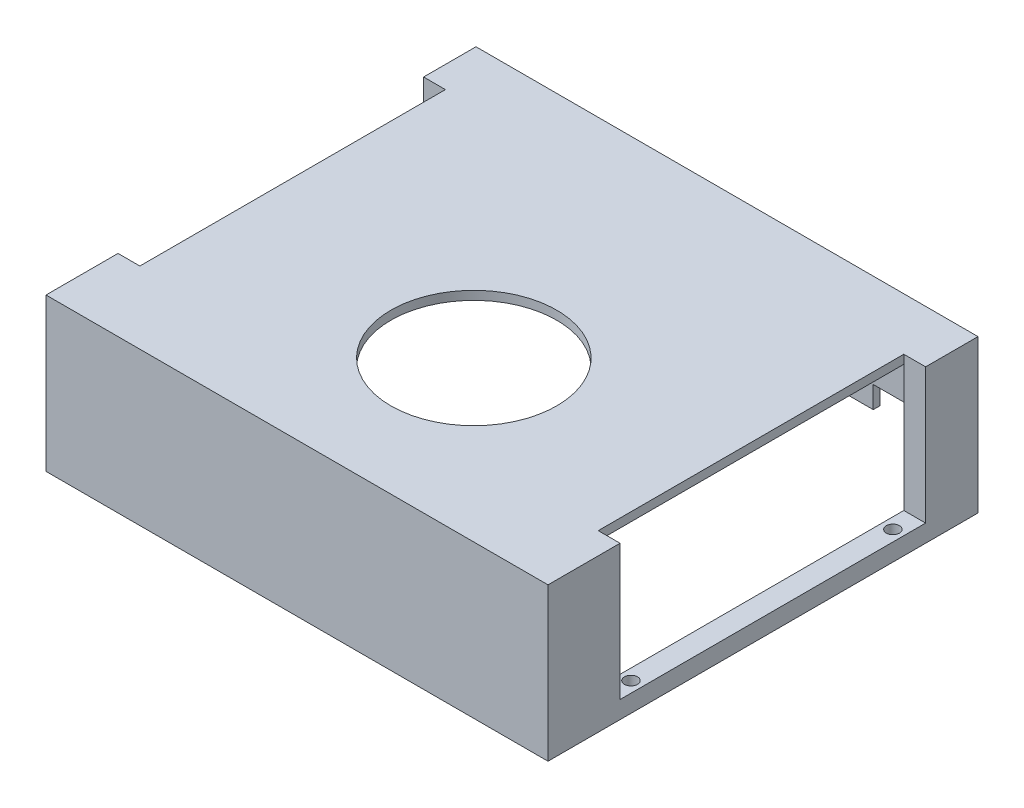
SolidWorks part; units mm, degrees
ref_plane "前视基准面" through (0, 0, 0) normal (0, 0, 1) x (1, 0, 0)
ref_plane "上视基准面" through (0, 0, 0) normal (0, 1, 0) x (1, 0, 0)
ref_plane "右视基准面" through (0, 0, 0) normal (1, 0, 0) x (0, 0, -1)
other "Configuration Table"
sketch "草图1" plane through (0, 0, 0) normal (0, 1, 0) x (1, 0, 0)
  line L1 (-52.5, 55.5) -> (52.5, 55.5)
  line L2 (-52.5, 55.5) -> (-52.5, -36.5)
  line L3 (-52.5, -36.5) -> (52.5, -36.5)
  line L4 (52.5, 55.5) -> (52.5, -36.5)
  line L5 (-57.5, 57) -> (57.5, 57)
  line L6 (-57.5, 57) -> (-57.5, -41.5)
  line L7 (-57.5, -41.5) -> (57.5, -41.5)
  line L8 (57.5, 57) -> (57.5, -41.5)
extrude "凸台-拉伸1" add sketch "草图1" along normal blind 35 contours L6 L7 L8 L5
sketch "草图2" plane through (0, 0, 0) normal (0, -1, 0) x (1, 0, 0)
  line L1 (-52.5, 36.5) -> (52.5, 36.5)
  line L2 (-52.5, 36.5) -> (-52.5, -55.5)
  line L3 (-52.5, -55.5) -> (52.5, -55.5)
  line L4 (52.5, 36.5) -> (52.5, -55.5)
extrude "切除-拉伸1" cut sketch "草图2" against normal blind 33
sketch "草图4" plane through (0, 0, 0) normal (0, -1, 0) x (-1, 0, 0)
  circle A0 centre (55, -20) radius 1.5
  circle A2 centre (55, 40) radius 1.5
  circle A3 centre (-55, -20) radius 1.5
  circle A4 centre (-55, 40) radius 1.5
extrude "切除-拉伸2" cut sketch "草图4" against normal blind 3
extrude "切除-拉伸3" cut sketch "草图4<2>" against normal blind 4
sketch "草图4<2>" plane through (0, 0, 0) normal (0, -1, 0) x (-1, 0, 0) same geometry as "草图4"
sketch "草图5" plane through (0, 35, 0) normal (0, 1, 0) x (1, 0, 0)
  line L0 (57.5, 57) -> (57.5, -41.5) construction
  line L1 (-57.5, 45) -> (-52.5, 45)
  line L2 (-57.5, 45) -> (-57.5, -25)
  line L3 (-57.5, -25) -> (-52.5, -25)
  line L4 (-52.5, 45) -> (-52.5, -25)
  line L5 (52.5, 45) -> (57.5, 45)
  line L6 (52.5, 45) -> (52.5, -25)
  line L7 (52.5, -25) -> (57.5, -25)
  line L8 (57.5, 45) -> (57.5, -25)
extrude "切除-拉伸4" cut sketch "草图5" against normal blind 31
sketch "草图6" plane through (0, 35, 0) normal (0, 1, 0) x (1, 0, 0)
  circle A0 centre (4, -5) radius 19
extrude "切除-拉伸5" cut sketch "草图6" against normal blind 2
sketch "草图7" plane through (0, 0, -57) normal (0, 0, -1) x (-1, 0, 0)
  line L0 (57.5, 0) -> (-57.5, 0) construction
  line L1 (-50, 0) -> (50, 0)
  line L2 (-50, 0) -> (-50, 10)
  line L3 (-35, 10) -> (-15, 10)
  line L4 (50, 0) -> (50, 10)
  line L5 (36, 10) -> (50, 10)
  line L7 (-50, 10) -> (-50, 15)
  line L8 (-50, 15) -> (-35, 15)
  line L9 (-35, 10) -> (-35, 15)
  line L11 (-15, 10) -> (-15, 20)
  line L12 (-15, 20) -> (36, 20)
  line L13 (36, 10) -> (36, 20)
extrude "切除-拉伸6" cut sketch "草图7" against normal blind 2
extrude "凸台-拉伸2" add sketch "草图6<3>" against normal blind 2
sketch "草图6<3>" plane through (0, 35, 0) normal (0, 1, 0) x (1, 0, 0) same geometry as "草图6"
extrude "切除-拉伸7" cut sketch "草图6<5>" against normal blind 2
sketch "草图6<5>" plane through (0, 35, 0) normal (0, 1, 0) x (1, 0, 0) same geometry as "草图6"
